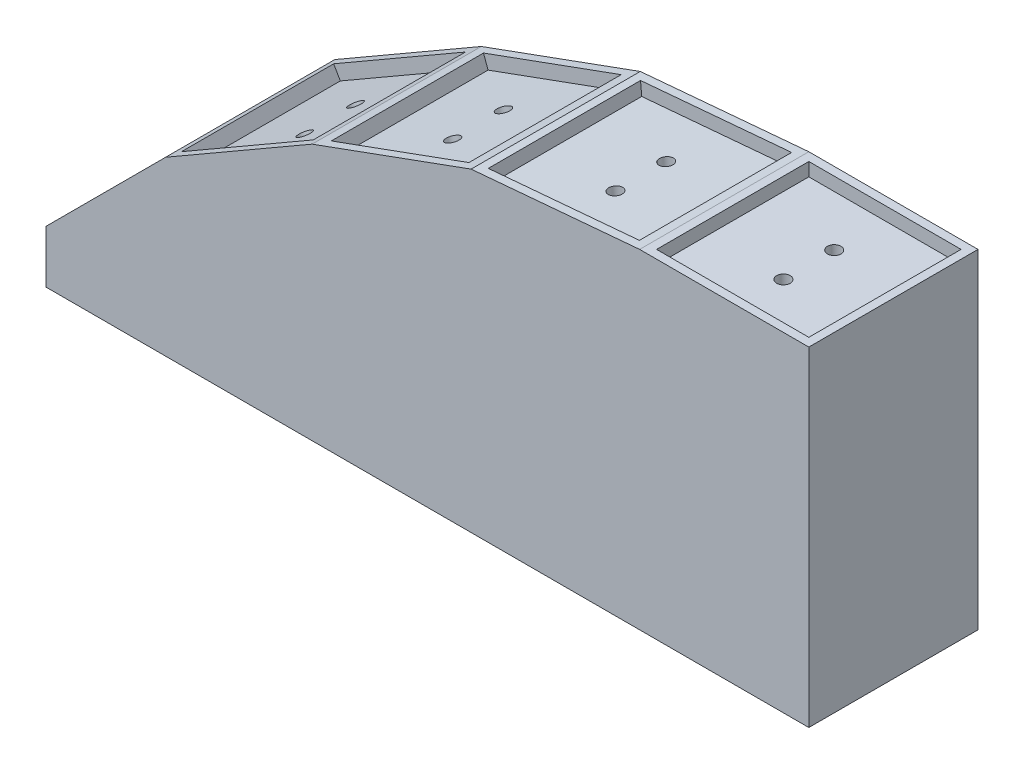
SolidWorks part; units mm, degrees
other "Markup1"
sketch "Sketch34" plane through (-281.715, -69.8831, -95.2498) normal (-0.9907, 0.0223, -0.134) x (-0.0947, 0.5934, 0.7993)
ref_plane "Front Plane" through (0, 0, 0) normal (0, 0, 1) x (1, 0, 0)
ref_plane "Top Plane" through (0, 0, 0) normal (0, 1, 0) x (1, 0, 0)
ref_plane "Right Plane" through (0, 0, 0) normal (1, 0, 0) x (0, 0, -1)
sketch "Sketch1" plane through (0, 0, 0) normal (0, 1, 0) x (1, 0, 0)
  line L1 (0, 0) -> (127, 0)
  line L2 (0, 0) -> (0, 127)
  line L3 (0, 127) -> (127, 127)
  line L4 (127, 0) -> (127, 127)
  line L5 (6.35, 120.65) -> (120.65, 120.65)
  line L6 (6.35, 120.65) -> (6.35, 6.35)
  line L7 (6.35, 6.35) -> (120.65, 6.35)
  line L8 (120.65, 120.65) -> (120.65, 6.35)
  dimension "D1" = 114.3
  dimension "D2" = 114.3
  dimension "D3" = 6.35
  dimension "D4" = 6.35
  dimension "D5" = 6.35
  dimension "D6" = 6.35
extrude "Boss-Extrude1" add sketch "Sketch1" along normal blind 10
ref_plane "Plane1" through (-0.8682, 9.924, 0) normal (-0.0872, 0.9962, 0) x (0, 0, 1)
sketch "Sketch18" plane through (-0.8682, 9.924, 0) normal (-0.0872, 0.9962, 0) x (0, 0, 1)
  line L1 (-127, 0.8716) -> (0, 0.8716)
  line L2 (-127, 0.8716) -> (-127, -126.1284)
  line L3 (-127, -126.1284) -> (0, -126.1284)
  line L4 (0, 0.8716) -> (0, -126.1284)
  dimension "D1" = 127
  dimension "D2" = 127
extrude "Boss-Extrude17" add sketch "Sketch18" against normal blind 10
ref_plane "Plane8" through (-14.4561, 39.7179, 0) normal (-0.342, 0.9397, 0) x (0, 0, 1)
sketch "Sketch20" plane through (-14.4561, 39.7179, 0) normal (-0.342, 0.9397, 0) x (0, 0, 1)
  line L1 (-127, -119.2524) -> (0, -119.2524)
  line L2 (-127, -119.2524) -> (-127, -246.2524)
  line L3 (-127, -246.2524) -> (0, -246.2524)
  line L4 (0, -119.2524) -> (0, -246.2524)
  dimension "D1" = 127
  dimension "D2" = 127
extrude "Boss-Extrude19" add sketch "Sketch20" against normal blind 10
sketch "Sketch21" plane through (-0.8682, 9.924, 0) normal (-0.0872, 0.9962, 0) x (0.9962, 0.0872, 0)
  line L0 (121.0624, 120.65) -> (7.1974, 120.65) construction
  line L1 (-119.561, 120.65) -> (-5.6959, 120.65)
  line L2 (-119.561, 120.65) -> (-119.561, 6.35)
  line L3 (-119.561, 6.35) -> (-5.6959, 6.35)
  line L4 (-5.6959, 120.65) -> (-5.6959, 6.35)
  line L5 (7.1974, 120.65) -> (7.1974, 6.35) construction
  line L6 (0.8716, 127) -> (-126.1284, 127) construction
  line L7 (-126.1284, 127) -> (-126.1284, 0) construction
  point P10 (-62.6284, 127)
  point P11 (-62.6284, 120.65)
  point P14 (-126.1284, 63.5)
  point P15 (-119.561, 63.5)
extrude "Cut-Extrude1" cut sketch "Sketch21" against normal blind 10
sketch "Sketch22" plane through (-14.4561, 39.7179, 0) normal (-0.342, 0.9397, 0) x (0.9397, 0.342, 0)
  line L0 (-246.2524, 127) -> (-246.2524, 0) construction
  line L1 (-237.745, 120.65) -> (-127.7598, 120.65)
  line L2 (-237.745, 120.65) -> (-237.745, 6.35)
  line L3 (-237.745, 6.35) -> (-127.7598, 6.35)
  line L4 (-127.7598, 120.65) -> (-127.7598, 6.35)
  line L5 (-119.2524, 127) -> (-246.2524, 127) construction
  line L6 (-2.9235, 120.65) -> (-112.9087, 120.65) construction
  line L7 (-112.9087, 120.65) -> (-112.9087, 6.35) construction
  point P6 (-246.2524, 63.5)
  point P7 (-237.745, 63.5)
  point P10 (-182.7524, 127)
  point P11 (-182.7524, 120.65)
extrude "Cut-Extrude2" cut sketch "Sketch22" against normal blind 10
sketch "Sketch23" plane through (0, 0, 0) normal (0, -1, 0) x (1, 0, 0)
  line L1 (0, 0) -> (127, 0)
  line L2 (0, 0) -> (0, -127)
  line L3 (0, -127) -> (127, -127)
  line L4 (127, 0) -> (127, -127)
extrude "Boss-Extrude21" add sketch "Sketch23" along normal blind 10
sketch "Sketch24" plane through (0.0033, -0.0379, 0) normal (0.0872, -0.9962, 0) x (0.9962, 0.0872, 0)
  line L0 (-124.8119, 0) -> (-0.0033, 0) construction
  line L1 (-124.8119, 0) -> (2.1881, 0)
  line L2 (-124.8119, 0) -> (-124.8119, -127)
  line L3 (-124.8119, -127) -> (2.1881, -127)
  line L4 (2.1881, 0) -> (2.1881, -127)
  line L5 (-0.0033, -127) -> (-124.8119, -127) construction
  dimension "D1" = 127
extrude "Boss-Extrude24" add sketch "Sketch24" along normal blind 10
sketch "Sketch25" plane through (-11.0359, 30.321, 0) normal (0.342, -0.9397, 0) x (0.9397, 0.342, 0)
  line L0 (-246.2524, -127) -> (-246.2524, 0) construction
  line L1 (-246.2524, 0) -> (-119.2524, 0)
  line L2 (-246.2524, 0) -> (-246.2524, -127)
  line L3 (-246.2524, -127) -> (-119.2524, -127)
  line L4 (-119.2524, 0) -> (-119.2524, -127)
  dimension "D1" = 127
  dimension "D2" = 127
extrude "Boss-Extrude25" add sketch "Sketch25" along normal blind 10
ref_plane "Plane9" through (-42.193, 73.0805, 0) normal (-0.5, 0.866, 0) x (0, 0, 1)
sketch "Sketch26" plane through (-42.193, 73.0805, 0) normal (-0.5, 0.866, 0) x (0, 0, 1)
  line L1 (-127, -235.1717) -> (0, -235.1717)
  line L2 (-127, -235.1717) -> (-127, -362.1717)
  line L3 (-127, -362.1717) -> (0, -362.1717)
  line L4 (0, -235.1717) -> (0, -362.1717)
  dimension "D1" = 127
  dimension "D2" = 127
extrude "Boss-Extrude26" add sketch "Sketch26" against normal blind 10
sketch "Sketch27" plane through (-42.193, 73.0805, 0) normal (-0.5, 0.866, 0) x (0.866, 0.5, 0)
  line L0 (-235.1717, 127) -> (-362.1717, 127) construction
  line L1 (-355.8217, 120.65) -> (-241.5217, 120.65)
  line L2 (-355.8217, 120.65) -> (-355.8217, 6.35)
  line L3 (-355.8217, 6.35) -> (-241.5217, 6.35)
  line L4 (-241.5217, 120.65) -> (-241.5217, 6.35)
  line L5 (-362.1717, 127) -> (-362.1717, 0) construction
  point P6 (-298.6717, 127)
  point P7 (-298.6717, 120.65)
  point P10 (-362.1717, 63.5)
  point P11 (-355.8217, 63.5)
  dimension "D1" = 114.3
  dimension "D2" = 114.3
extrude "Cut-Extrude3" cut sketch "Sketch27" against normal blind 10
sketch "Sketch28" plane through (-37.193, 64.4202, 0) normal (0.5, -0.866, 0) x (0.866, 0.5, 0)
  line L1 (-362.1717, 0) -> (-235.1717, 0)
  line L2 (-362.1717, 0) -> (-362.1717, -127)
  line L3 (-362.1717, -127) -> (-235.1717, -127)
  line L4 (-235.1717, 0) -> (-235.1717, -127)
  dimension "D1" = 127
  dimension "D2" = 127
extrude "Boss-Extrude27" add sketch "Sketch28" along normal blind 10
ref_plane "Plane10" through (-123.9188, 123.9188, 0) normal (-0.7071, 0.7071, 0) x (0, 0, 1)
sketch "Sketch29" plane through (-123.9188, 123.9188, 0) normal (-0.7071, 0.7071, 0) x (0, 0, 1)
  line L1 (-127, -327.9902) -> (0, -327.9902)
  line L2 (-127, -327.9902) -> (-127, -454.9902)
  line L3 (-127, -454.9902) -> (0, -454.9902)
  line L4 (0, -327.9902) -> (0, -454.9902)
  dimension "D1" = 127
  dimension "D2" = 127
extrude "Boss-Extrude28" add sketch "Sketch29" against normal blind 10
sketch "Sketch30" plane through (-123.9188, 123.9188, 0) normal (-0.7071, 0.7071, 0) x (0, 0, 1)
  line L0 (-127, -454.9902) -> (0, -454.9902) construction
  line L1 (-120.65, -334.3402) -> (-6.35, -334.3402)
  line L2 (-120.65, -334.3402) -> (-120.65, -448.6402)
  line L3 (-120.65, -448.6402) -> (-6.35, -448.6402)
  line L4 (-6.35, -334.3402) -> (-6.35, -448.6402)
  line L5 (-127, -327.9902) -> (-127, -454.9902) construction
  point P6 (-63.5, -454.9902)
  point P7 (-63.5, -448.6402)
  point P10 (-127, -391.4902)
  point P11 (-120.65, -391.4902)
  dimension "D1" = 114.3
  dimension "D2" = 114.3
extrude "Cut-Extrude4" cut sketch "Sketch30" against normal blind 10
sketch "Sketch31" plane through (-116.8477, 116.8477, 0) normal (0.7071, -0.7071, 0) x (0, 0, -1)
  line L1 (0, -454.9902) -> (127, -454.9902)
  line L2 (0, -454.9902) -> (0, -327.9902)
  line L3 (0, -327.9902) -> (127, -327.9902)
  line L4 (127, -454.9902) -> (127, -327.9902)
  dimension "D1" = 127
  dimension "D2" = 127
extrude "Boss-Extrude29" add sketch "Sketch31" along normal blind 10
sketch "Sketch32" plane through (0, 0, 0) normal (0, 0, 1) x (1, 0, 0)
  line L1 (127, -237.35) -> (127, -10)
  line L2 (127, -10) -> (0.8732, -10)
  line L3 (0.8732, -10) -> (-122.1506, -20.7632)
  line L4 (-122.1506, -20.7632) -> (-237.373, -62.7007)
  line L5 (-237.373, -62.7007) -> (-343.5626, -124.0093)
  line L6 (-343.5626, -124.0093) -> (-431.5033, -211.95)
  line L11 (127, -237.35) -> (-445.6455, -237.35)
  line L12 (-445.6455, -237.35) -> (-445.6455, -197.8079)
  line L13 (-445.6455, -197.8079) -> (-431.5033, -211.95)
  dimension "D1" = 25.4
extrude "Boss-Extrude30" add sketch "Sketch32" against normal up to surface (127 mm away) up to face at (-171.1316, -64.2342, -127)
sketch "Sketch33" plane through (0, 0, -127) normal (0, 0, -1) x (-1, 0, 0)
  line L0 (-127, 10) -> (-127, -237.35) construction
  line L1 (-127, 10) -> (0, 10) construction
  line L2 (0, 10) -> (126.5167, -1.0688) construction
  line L3 (126.5167, -1.0688) -> (245.8577, -44.5053) construction
  line L4 (245.8577, -44.5053) -> (355.8429, -108.0053) construction
  line L5 (355.8429, -108.0053) -> (445.6455, -197.8079) construction
  text T0 "0"
  text T1 "5"
  text T2 "15\r\n"
  text T3 "30\r\n"
  text T4 "45\r\n"
  dimension "D1" = 63.5
  dimension "D2" = 12.7
  dimension "D3" = 12.7
  dimension "D4" = 190.5
  dimension "D5" = 12.7
  dimension "D6" = 317.5
  dimension "D7" = 12.7
  dimension "D8" = 419.1
  dimension "D9" = 12.7
  dimension "D10" = 520.7
extrude "Cut-Extrude5" cut sketch "Sketch33" against normal blind 2.54
scale "Scale5" scale about centroid uniform scaling yes scale factor 0.5
sketch "Sketch35" plane through (0, -66.7667, 0) normal (0, 1, 0) x (1, 0, 0)
  line L0 (4.7218, 34.9249) -> (4.7218, 92.0749) construction
  line L1 (4.7218, 92.0749) -> (-52.4282, 92.0749) construction
  line L2 (-52.4282, 34.9249) -> (4.7218, 34.9249) construction
  circle A0 centre (-23.8532, 73.0249) radius 2.5273
  circle A1 centre (-23.8532, 53.9749) radius 2.5273
  dimension "D1" = 5.0546
  dimension "D2" = 28.575
  dimension "D3" = 19.05
  dimension "D4" = 19.05
extrude "Cut-Extrude6" cut sketch "Sketch35" against normal blind 9
sketch "Sketch36" plane through (5.3762, -61.4507, 0) normal (-0.0872, 0.9962, 0) x (0.9962, 0.0872, 0)
  line L0 (-64.0587, 92.0749) -> (-120.9912, 92.0749) construction
  line L1 (-120.9912, 34.9249) -> (-64.0587, 34.9249) construction
  line L2 (-64.0587, 34.9249) -> (-64.0587, 92.0749) construction
  circle A0 centre (-92.6337, 73.0249) radius 2.5273
  circle A1 centre (-92.6337, 53.9749) radius 2.5273
  dimension "D1" = 5.0546
  dimension "D2" = 19.05
  dimension "D3" = 19.05
  dimension "D4" = 28.575
extrude "Cut-Extrude7" cut sketch "Sketch36" against normal blind 9
sketch "Sketch37" plane through (9.4361, -25.9254, 0) normal (-0.342, 0.9397, 0) x (0.9397, 0.342, 0)
  line L0 (-138.9654, 92.0749) -> (-193.958, 92.0749) construction
  line L1 (-193.958, 34.9249) -> (-138.9654, 34.9249) construction
  line L2 (-138.9654, 34.9249) -> (-138.9654, 92.0749) construction
  circle A0 centre (-167.5404, 73.0249) radius 2.5273
  circle A1 centre (-167.5404, 53.9749) radius 2.5273
  dimension "D1" = 5.0546
  dimension "D2" = 19.05
  dimension "D3" = 19.05
  dimension "D4" = 28.575
extrude "Cut-Extrude8" cut sketch "Sketch37" against normal blind 9
sketch "Sketch38" plane through (-3.5865, 6.212, 0) normal (-0.5, 0.866, 0) x (0.866, 0.5, 0)
  line L1 (-202.298, 92.0749) -> (-259.448, 92.0749) construction
  line L2 (-259.448, 34.9249) -> (-202.298, 34.9249) construction
  line L3 (-202.298, 34.9249) -> (-202.298, 92.0749) construction
  circle A0 centre (-230.873, 73.0249) radius 2.5273
  circle A1 centre (-230.873, 53.9749) radius 2.5273
  dimension "D1" = 5.0546
  dimension "D2" = 19.05
  dimension "D3" = 19.05
  dimension "D4" = 28.575
extrude "Cut-Extrude9" cut sketch "Sketch38" against normal blind 9
sketch "Sketch39" plane through (-52.8421, 52.8421, 0) normal (-0.7071, 0.7071, 0) x (0, 0, 1)
  line L0 (-92.0749, -253.6987) -> (-92.0749, -310.8487) construction
  line L1 (-34.9249, -310.8487) -> (-34.9249, -253.6987) construction
  line L2 (-34.9249, -253.6987) -> (-92.0749, -253.6987) construction
  circle A0 centre (-73.0249, -282.2737) radius 2.5273
  circle A1 centre (-53.9749, -282.2737) radius 2.5273
  dimension "D1" = 5.0546
  dimension "D2" = 19.05
  dimension "D3" = 19.05
  dimension "D4" = 28.575
extrude "Cut-Extrude10" cut sketch "Sketch39" against normal blind 9
